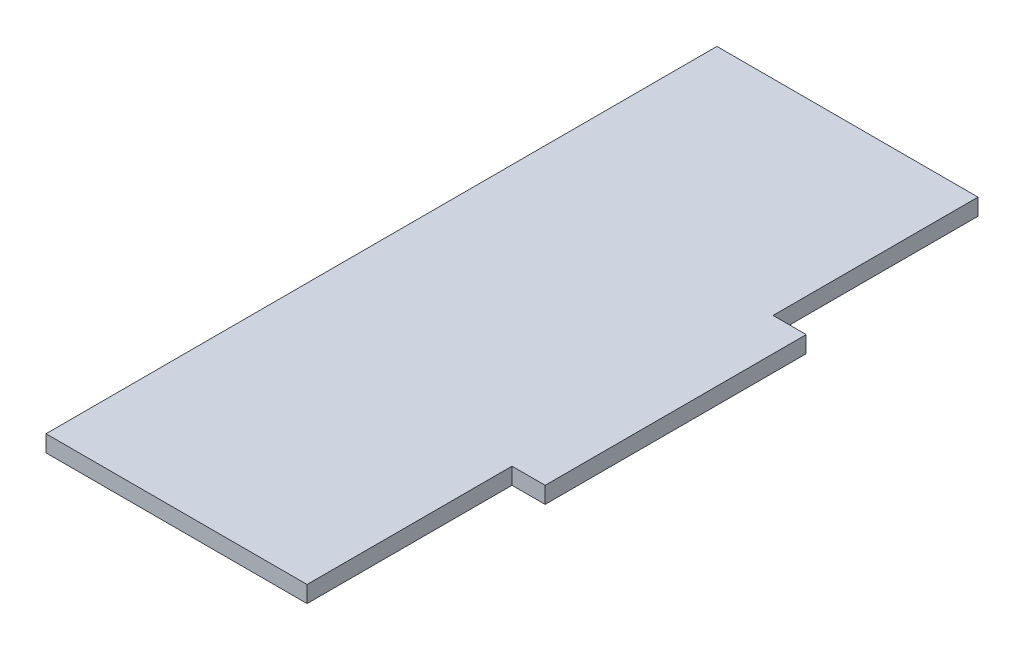
SolidWorks part; units mm, degrees
material "Cedar"
ref_plane "Front Plane" through (0, 0, 0) normal (0, 0, 1) x (1, 0, 0)
ref_plane "Top Plane" through (0, 0, 0) normal (0, 1, 0) x (1, 0, 0)
ref_plane "Right Plane" through (0, 0, 0) normal (1, 0, 0) x (0, 0, -1)
sketch "Sketch1" plane through (0, 0, 0) normal (0, 1, 0) x (1, 0, 0)
  line L0 (-25, 39.25) -> (25, 39.25)
  line L1 (25, 39.25) -> (25, 0)
  line L2 (25, 0) -> (31.35, 0)
  line L3 (31.35, 0) -> (31.35, -50)
  line L4 (31.35, -50) -> (25, -50)
  line L5 (25, -50) -> (25, -89.25)
  line L6 (25, -89.25) -> (-25, -89.25)
  line L7 (-25, -89.25) -> (-25, -50)
  line L8 (-25, -50) -> (-31.35, -50)
  line L9 (-31.35, -50) -> (-31.35, 0)
  line L10 (-31.35, 0) -> (-25, 0)
  line L11 (-25, 0) -> (-25, 39.25)
  line L12 (-25, 0) -> (-25, -50) construction
  point P11 (0, 39.25)
  point P14 (-31.35, -25)
  dimension "D1" = 6.35
  dimension "D2" = 50
  dimension "D3" = 50
  dimension "D4" = 128.5
extrude "Boss-Extrude1" add sketch "Sketch1" along normal blind 3.175 contours L11 L12 L7 L6 L5 L4 L3 L2 L1 L0 region at (1.3267, 0, 25)
equation "\"length\" = 128.5mm"
equation "\"w_mach\" = 50mm"
equation "\"w_tab\"= 50mm"
equation "\"t_wood\"= 0.125in"
equation "\"t_side\"= 0.25in"
equation "\"D1@Sketch1\"=\"t_side\""
equation "\"D2@Sketch1\"=\"w_tab\""
equation "\"D3@Sketch1\"=\"w_mach\""
equation "\"D4@Sketch1\"=\"length\""
equation "\"D1@Boss-Extrude1\"=\"t_wood\""
